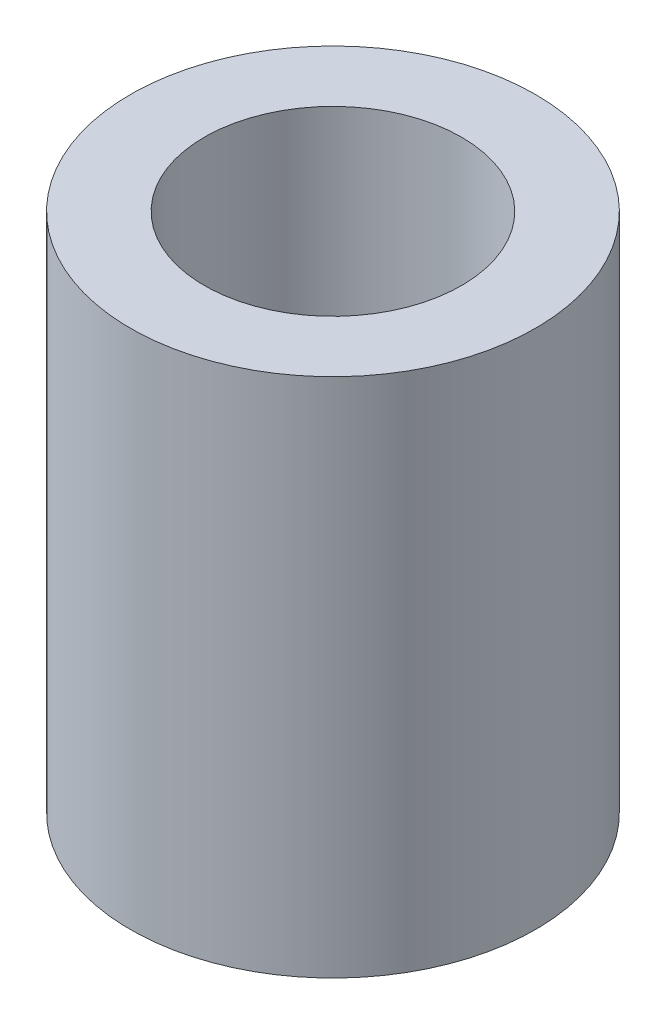
SolidWorks part; units mm, degrees
material "Brass"
ref_plane "Front Plane" through (0, 0, 0) normal (0, 0, 1) x (1, 0, 0)
ref_plane "Top Plane" through (0, 0, 0) normal (0, 1, 0) x (1, 0, 0)
ref_plane "Right Plane" through (0, 0, 0) normal (1, 0, 0) x (0, 0, -1)
sketch "Sketch1" plane through (0, 0, 0) normal (0, 0, 1) x (1, 0, 0)
  line L0 (0, 0) -> (0, 8.1) construction
  line L2 (2, 8.1) -> (2, 0)
  line L4 (2, 8.1) -> (3.15, 8.1)
  line L5 (3.15, 8.1) -> (3.15, 0)
  line L7 (3.15, 0) -> (2, 0)
  dimension "D1" = 8.1
  dimension "D2" = 2
  dimension "D3" = 3.15
revolve "Revolve1" add sketch "Sketch1" angle 360 about L0
move or copy body "Body-Move/Copy4" [suppressed] bodies to move or copy 101 parameters "D1"=0, "D2"=0, "D3"=0
move or copy body "Body-Move/Copy3" [suppressed] bodies to move or copy 101 parameters "D1"=0, "D2"=0, "D3"=0
move or copy body "Body-Move/Copy2" [suppressed] bodies to move or copy 101 parameters "D1"=0, "D2"=0, "D3"=0
move or copy body "Body-Move/Copy1" [suppressed] bodies to move or copy 101 parameters "D1"=0, "D2"=0, "D3"=0
